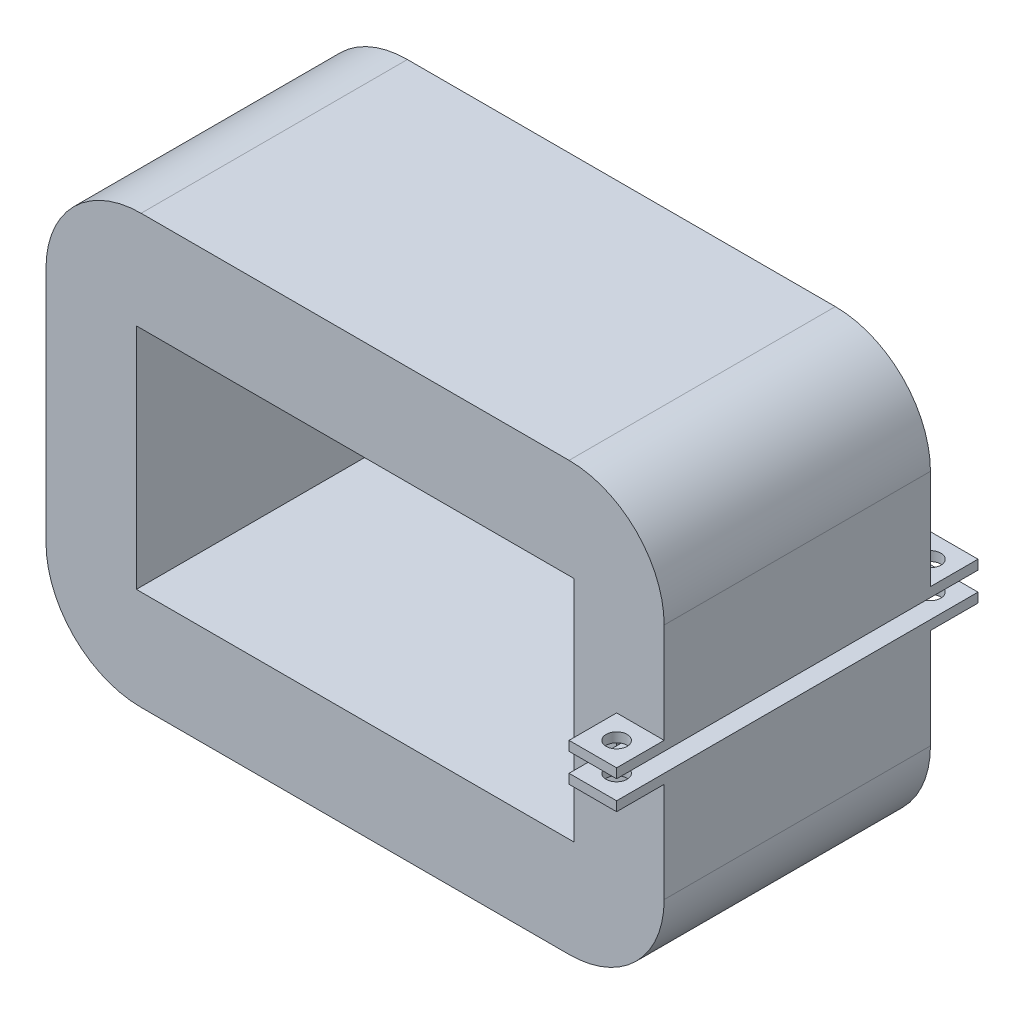
SolidWorks part; units mm, degrees
ref_plane "前基準面" through (0, 0, 0) normal (0, 0, 1) x (1, 0, 0)
ref_plane "上基準面" through (0, 0, 0) normal (0, 1, 0) x (1, 0, 0)
ref_plane "右基準面" through (0, 0, 0) normal (1, 0, 0) x (0, 0, -1)
sketch "草圖1" plane through (0, 0, 0) normal (0, 0, 1) x (1, 0, 0)
  line L0 (-9.02, 0) -> (7.9922, 0) construction
  line L2 (-59.9347, 22.5) -> (5.0653, 22.5)
  line L3 (-59.9347, 22.5) -> (-59.9347, -22.5)
  line L4 (-59.9347, -22.5) -> (5.0653, -22.5)
  line L5 (5.0653, 22.5) -> (5.0653, -22.5)
  dimension "D1" = 45
  dimension "D2" = 22.5
  dimension "D3" = 65
extrude "填料-伸長1" add sketch "草圖1" along normal blind 28
sketch "草圖2" plane through (0, 0, 0) normal (0, 0, 1) x (1, 0, 0)
  line L0 (-59.9347, 0) -> (5.361, 0) construction
  line L1 (-59.9347, 22.5) -> (-59.9347, -22.5) construction
  line L2 (-27.4347, 22.5) -> (-27.4347, -22.5) construction
  line L3 (5.0653, 22.5) -> (-59.9347, 22.5) construction
  line L4 (-59.9347, -22.5) -> (5.0653, -22.5) construction
  line L6 (-50.4347, 12) -> (-4.4347, 12)
  line L7 (-50.4347, 12) -> (-50.4347, -12)
  line L8 (-50.4347, -12) -> (-4.4347, -12)
  line L9 (-4.4347, 12) -> (-4.4347, -12)
  dimension "D1" = 46
  dimension "D2" = 24
  dimension "D3" = 9.5
  dimension "D4" = 10.5
extrude "除料-伸長1" cut sketch "草圖2" along normal blind 39
ref_plane "平面1" through (0, 0, 28) normal (0, 0, 1) x (1, 0, 0)
sketch "草圖3" plane through (0, 0, 28) normal (0, 0, 1) x (1, 0, 0)
  line L0 (-59.9347, 22.5) -> (-59.9347, -22.5) construction
  line L2 (-59.9347, 12) -> (-55.9347, 12)
  line L3 (-59.9347, 12) -> (-59.9347, -12)
  line L4 (-59.9347, -12) -> (-55.9347, -12)
  line L5 (-55.9347, 12) -> (-55.9347, -12)
  line L6 (-50.4347, 12) -> (-4.4347, 12) construction
  dimension "D1" = 4
  dimension "D2" = 24
  dimension "D3" = 0
ref_plane "平面2" through (-59.9347, 0, 0) normal (-1, 0, 0) x (0, 0, 1)
sketch "草圖6" plane through (0, 0, 28) normal (0, 0, 1) x (1, 0, 0)
  line L0 (-14.4347, 0) -> (5.0653, -22.5)
  line L1 (-4.4347, 12) -> (-4.4347, -12) construction
  line L2 (-4.4347, -12) -> (-50.4347, -12) construction
  line L3 (-14.4347, 0) -> (-14.4347, -22.5)
  line L4 (-59.9347, -22.5) -> (5.0653, -22.5) construction
  line L5 (-14.4347, -22.5) -> (5.0653, -22.5)
  dimension "D1" = 10
  dimension "D2" = 12
ref_plane "平面4" through (0, 0, 0) normal (0, 0, -1) x (-1, 0, 0)
fillet "圓角1" radius 10 1 edges at (-59.9347, -22.5, 14) type face fillet first side face at (-59.9347, 0, 14) second side face at (-27.4347, -22.5, 14)
fillet "圓角2" radius 10 1 edges at (-59.9347, 22.5, 14) type face fillet first side face at (-27.4347, 22.5, 14) second side face at (-59.9347, 5, 14)
fillet "圓角3" radius 10 1 edges at (5.0653, 22.5, 14) type face fillet first side face at (-22.4347, 22.5, 14) second side face at (5.0653, 0, 14)
fillet "圓角4" radius 10 1 edges at (5.0653, -22.5, 14) type face fillet first side face at (-22.4347, -22.5, 14) second side face at (5.0653, -5, 14)
ref_plane "平面5" through (0, 0, 0) normal (0, 1, 0) x (1, 0, 0)
sketch "草圖9" plane through (0, 0, 0) normal (0, 1, 0) x (1, 0, 0)
  line L0 (5.0653, 0) -> (5.0653, -28) construction
  line L1 (0.0653, 3.3121) -> (5.0653, 3.3121)
  line L2 (0.0653, 3.3121) -> (0.0653, -30.7585)
  line L3 (0.0653, -30.7585) -> (5.0653, -30.7585)
  line L4 (5.0653, 3.3121) -> (5.0653, -30.7585)
  dimension "D1" = 5
  dimension "D2" = 5
extrude "除料-伸長2" cut sketch "草圖9" against normal blind 1 and the other way blind 1
sketch "草圖10" plane through (0, 0, 0) normal (0, 0, 1) x (1, 0, 0)
  line L0 (5.0653, -12.5) -> (5.0653, -1) construction
  line L1 (0.0653, -1) -> (5.0653, -1)
  line L2 (0.0653, -1) -> (0.0653, -2)
  line L3 (0.0653, -2) -> (5.0653, -2)
  line L4 (5.0653, -1) -> (5.0653, -2)
  line L5 (5.0653, 1) -> (5.0653, 12.5) construction
  line L6 (0.0653, 1) -> (5.0653, 1)
  line L7 (0.0653, 1) -> (0.0653, 2)
  line L8 (0.0653, 2) -> (5.0653, 2)
  line L9 (5.0653, 1) -> (5.0653, 2)
  dimension "D1" = 1
  dimension "D2" = 1
extrude "填料-伸長5" add sketch "草圖10" against normal blind 5
ref_plane "平面6" through (0, -2, 0) normal (0, -1, 0) x (-1, 0, 0)
sketch "草圖12" plane through (0, -2, 0) normal (0, -1, 0) x (-1, 0, 0)
  line L0 (-5.0653, 2.5) -> (-0.0653, 2.5) construction
  line L1 (-5.0653, 5) -> (-5.0653, 0) construction
  line L2 (-0.0653, 5) -> (-0.0653, 0) construction
  line L3 (-2.5653, 5) -> (-2.5653, 0) construction
  line L4 (-0.0653, 5) -> (-5.0653, 5) construction
  line L5 (24.75, 0) -> (-24.75, 0) construction
  circle A0 centre (-2.5653, 2.5) radius 1.1
  dimension "D1" = 2.2
extrude "除料-伸長3" cut sketch "草圖12" against normal blind 5 contours A0
pattern_linear "直線複製排列1" count 2 spacing 33 along (0, 0, 1) of "填料-伸長5"
pattern_linear "直線複製排列2" count 2 spacing 33 along (0, 0, 1) of "除料-伸長3"
